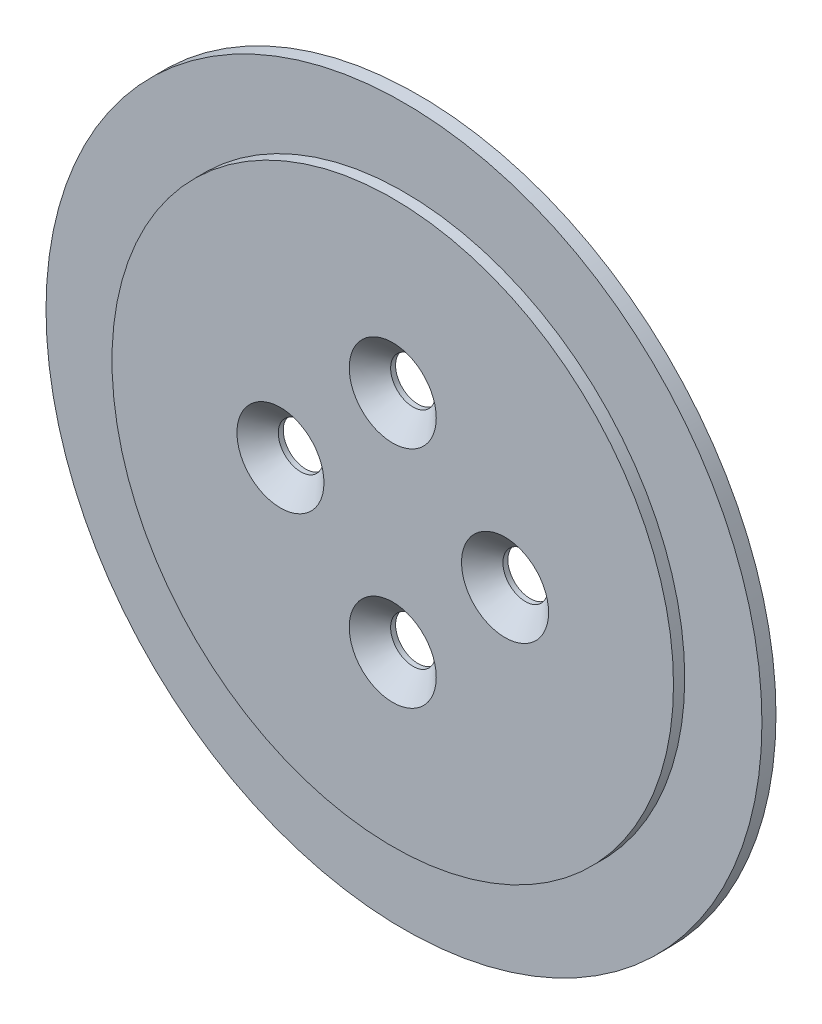
SolidWorks part; units mm, degrees
ref_plane "Front Plane" through (0, 0, 0) normal (0, 0, 1) x (1, 0, 0)
ref_plane "Top Plane" through (0, 0, 0) normal (0, 1, 0) x (1, 0, 0)
ref_plane "Right Plane" through (0, 0, 0) normal (1, 0, 0) x (0, 0, -1)
sketch "Sketch1" plane through (0, 0, 0) normal (0, 0, 1) x (1, 0, 0)
  circle A0 centre (0, 0) radius 25.5
  circle A1 centre (0, 0) radius 20
  dimension "D1" = 51
  dimension "D2" = 40
extrude "Boss-Extrude1" add sketch "Sketch1" along normal blind 1 contours A0 A1 region at (-24.7788, 0, 0)
extrude "Boss-Extrude2" add sketch "Sketch1<3>" along normal blind 1.8 contours A1 region at (0, 0, 0)
sketch "Sketch1<3>" plane through (0, 0, 0) normal (0, 0, 1) x (1, 0, 0) same geometry as "Sketch1"
sketch "Sketch2" plane through (0, 0, 1.8) normal (0, 0, 1) x (1, 0, 0)
  line L0 (0, 0) -> (0, 8) construction
  circle A0 centre (0, 8) radius 1.75
  circle A1 centre (8, 0) radius 1.75
  circle A2 centre (0, -8) radius 1.75
  circle A3 centre (-8, 0) radius 1.75
  point P0 (0, 8)
  dimension "D2" = 3.5
  dimension "D1" = 8
  dimension "D3" = 4
hole_wizard "Hole1" positions "3DSketch1" profile "Sketch4" legacy end condition through all
sketch3d "3DSketch1"
  point P0 (-8, 0, 1.8)
  point P3 (0, 8, 1.8)
  point P6 (8, 0, 1.8)
  point P9 (0, -8, 1.8)
sketch "Sketch4" plane through (-8, 0, 1.8) normal (1, 0, 0) x (0, -1, 0)
  line L0 (0, 0) -> (0, 1.8)
  line L1 (0, 1.8) -> (1.6, 1.8)
  line L2 (1.6, 1.8) -> (1.6, 1.4485)
  line L3 (1.6, 1.4485) -> (3.1, 0)
  line L4 (3.1, 0) -> (0, 0)
  line L5 (0, -6.4453) -> (0, 115.525) construction
  line L6 (-1.6, 1.4485) -> (-3.1, 0) construction
  dimension "Diameter" = 3.2
  dimension "Depth" = 1.8
  dimension "C-Sink Angle" = 92
  dimension "C-Sink Diameter" = 6.2
